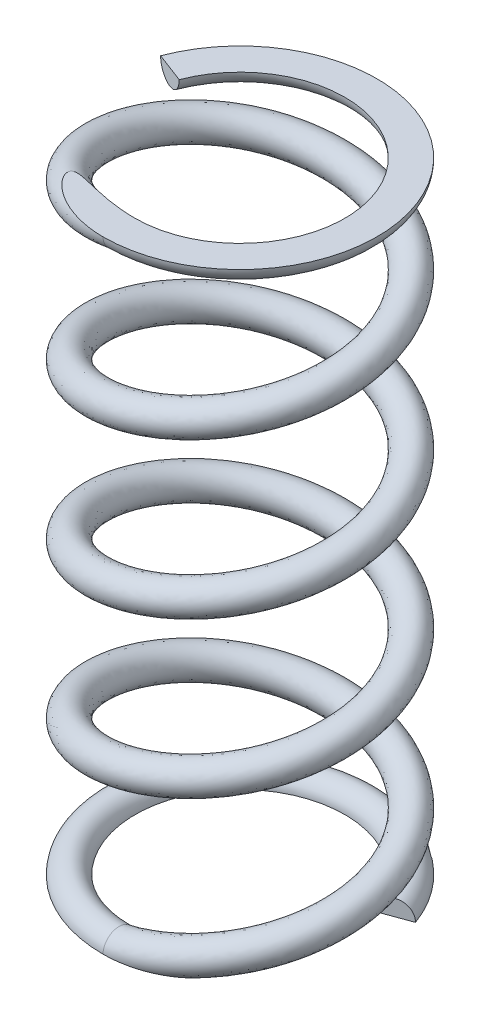
SolidWorks part; units mm, degrees
ref_plane "Front" through (0, 0, 0) normal (0, 0, 1) x (1, 0, 0)
ref_plane "Top" through (0, 0, 0) normal (0, 1, 0) x (1, 0, 0)
ref_plane "Right" through (0, 0, 0) normal (1, 0, 0) x (0, 0, -1)
ref_plane "Top Shock" through (0, 127, 0) normal (0, 1, 0) x (1, 0, 0)
ref_axis "Axis1" through (0, 129.1224, 0) along (0, -1, 0)
sketch "Cut" plane through (0, 0, 0) normal (0, 0, 1) x (1, 0, 0)
  line L0 (50, 127) -> (-50, 127) construction
  line L1 (-48.567, 150.0825) -> (54.9841, 150.0825)
  line L2 (-48.567, 150.0825) -> (-48.567, 127)
  line L3 (-48.567, 127) -> (54.9841, 127)
  line L4 (54.9841, 150.0825) -> (54.9841, 127)
  line L5 (50, 0) -> (-50, 0) construction
  line L6 (-48.567, 0) -> (54.9841, 0)
  line L7 (-48.567, 0) -> (-48.567, -30.0736)
  line L8 (-48.567, -30.0736) -> (54.9841, -30.0736)
  line L9 (54.9841, 0) -> (54.9841, -30.0736)
sketch "Helix" plane through (0, 0, 0) normal (0, 1, 0) x (1, 0, 0)
  line L0 (0, 0) -> (0, -24.72) construction
  circle A0 centre (0, 0) radius 24.72
  point P3 (0, -26.36)
  dimension "D1" = 24.72
sketch "Sketch3" plane through (0, 0, 0) normal (0, 1, 0) x (1, 0, 0)
  line L0 (0, 0) -> (23.2292, 8.4547) construction
  line L2 (0, 0) -> (0, -24.72) construction
  arc A0 (23.2292, 8.4547) -> (0, -24.72) centre (0, 0) ccw
  point P3 (0, -28)
  dimension "D1" = 24.72
  dimension "D2" = 110
sketch "Sketch5" plane through (0, 0, 0) normal (1, 0, 0) x (0, 0, -1)
  line L0 (-28, 0) -> (0, 0) construction
  circle A0 centre (-24.72, 0) radius 3.28
  dimension "D1" = 6.56
  dimension "D2" = 28
  dimension "D3" = 24.72
sketch "Sketch6" plane through (0, 127, 0) normal (0, 1, 0) x (1, 0, 0)
  line L0 (0, -0.5556) -> (0, -24.72) construction
  line L1 (0, -0.5556) -> (-23.108, 8.7806) construction
  arc A0 (0, -24.72) -> (-23.108, 8.7806) centre (0, 0) ccw
  point P3 (0, -24.72)
  dimension "D1" = 24.72
  dimension "D2" = 112
sketch "Sketch7" plane through (0, 0, 0) normal (1, 0, 0) x (0, 0, -1)
  circle A0 centre (-24.72, 127) radius 3.28
curve "Helix/Spiral3" pitch 31.75 height 127 radius 24.72 centre (0, 0, 0) axis (0, 1, 0) start towards (0, 0, 1)
sweep "Sweep7" add profiles "Sketch5" path "Helix/Spiral3"
sweep "Sweep8" add profiles "Sketch5<5>" path "Sketch3"
sketch "Sketch5<5>" plane through (0, 0, 0) normal (1, 0, 0) x (0, 0, -1) same geometry as "Sketch5"
sweep "Sweep9" add profiles "Sketch7" path "Sketch6"
extrude "Cut-Extrude3" cut sketch "Cut" against normal through all both and the other way through all
